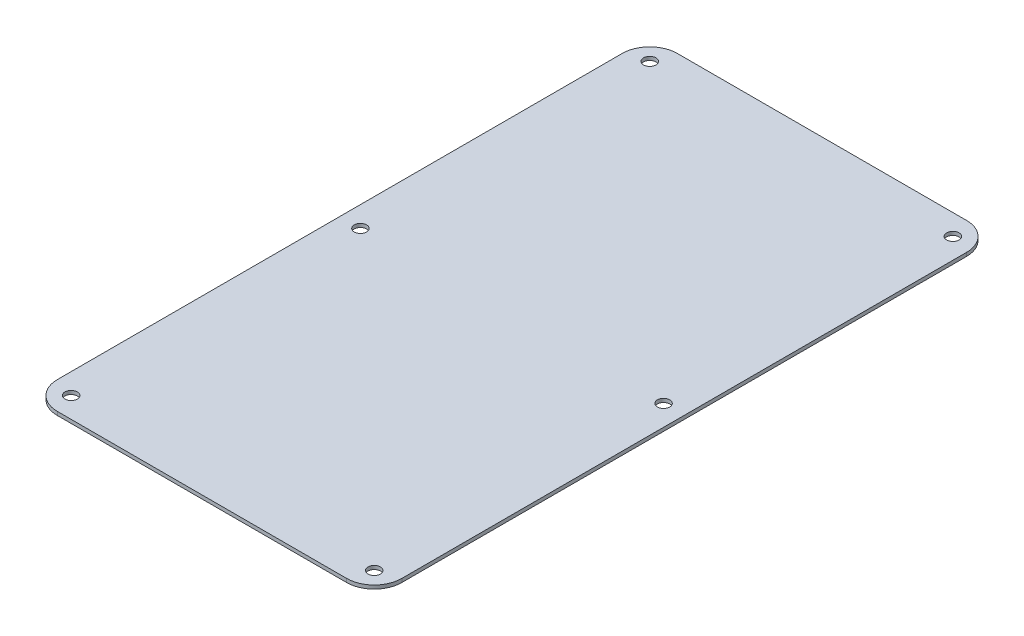
SolidWorks part; units mm, degrees
note: The reader was unsure of these and kept them because the rebuilt part matched: thickness of "Base-Flange1", "Sheet-Metal1", "Sheet-Metal2".
material "5052-H32"
ref_plane "Front Plane" through (0, 0, 0) normal (0, 0, 1) x (1, 0, 0)
ref_plane "Top Plane" through (0, 0, 0) normal (0, 1, 0) x (1, 0, 0)
ref_plane "Right Plane" through (0, 0, 0) normal (1, 0, 0) x (0, 0, -1)
sketch "Sketch1" plane through (0, 0, 0) normal (0, 1, 0) x (1, 0, 0)
  line L0 (53.8121, -95.6164) -> (-56.1879, 114.3836) construction
  line L1 (-63.6879, 121.8836) -> (61.3121, 121.8836)
  line L2 (-63.6879, 121.8836) -> (-63.6879, -103.1164)
  line L3 (-63.6879, -103.1164) -> (61.3121, -103.1164)
  line L4 (61.3121, 121.8836) -> (61.3121, -103.1164)
  line L5 (-63.6879, 121.8836) -> (61.3121, -103.1164) construction
  line L6 (-63.6879, -103.1164) -> (61.3121, 121.8836) construction
  point P0 (-1.1879, 9.3836)
  point P10 (-1.1879, 9.3836)
  dimension "D1" = 225
  dimension "D2" = 125
base flange "Base-Flange1" sketch "Sketch1" thickness 1.3 reverse thickness direction no parameters "D1"=1.016
sketch "Sketch6" plane through (0, 0, 0) normal (0, 1, 0) x (1, 0, 0)
  circle A0 centre (53.8121, 114.3836) radius 2.25
  circle A1 centre (53.8121, -95.6164) radius 2.25
  circle A2 centre (-56.1879, -95.6164) radius 2.25
  circle A3 centre (-56.1879, 114.3836) radius 2.25
  circle A4 centre (53.8121, 9.3836) radius 2.25
  circle A5 centre (-56.1879, 9.3836) radius 2.25
  dimension "D1" = 4.5
extrude "Cut-Extrude1" cut sketch "Sketch6" against normal blind 10 normal cut yes
fillet "Fillet1" radius 10 4 edges at (-63.6879, -0.65, -121.8836) (61.3121, -0.65, -121.8836) (-63.6879, -0.65, 103.1164) (61.3121, -0.65, 103.1164)
sketch "Bend-Lines1" [suppressed] plane through (0, 0, 0) normal (0, 1, 0) x (1, 0, 0)
sketch "Bounding-Box1" [suppressed] plane through (0, 0, 0) normal (0, 1, 0) x (1, 0, 0)
sheet metal parameters "Sheet-Metal1" thickness 1.3 parameters "D1"=1.016, "D7"=1.52
flat pattern "Flat-Pattern1" [suppressed]
sketch "Bend-Lines2" plane through (0, 0, 0) normal (0, 1, 0) x (1, 0, 0)
sketch "Bounding-Box2" [suppressed] plane through (0, 0, 0) normal (0, 1, 0) x (1, 0, 0)
sheet metal parameters "Sheet-Metal2" thickness 1.3 parameters "D1"=1.016, "D7"=1.52
flat pattern "Flat-Pattern1"
sketch "Bend-Lines2" plane through (0, 0, 0) normal (0, 1, 0) x (1, 0, 0)
sketch "Bounding-Box2" [suppressed] plane through (0, 0, 0) normal (0, 1, 0) x (1, 0, 0)
